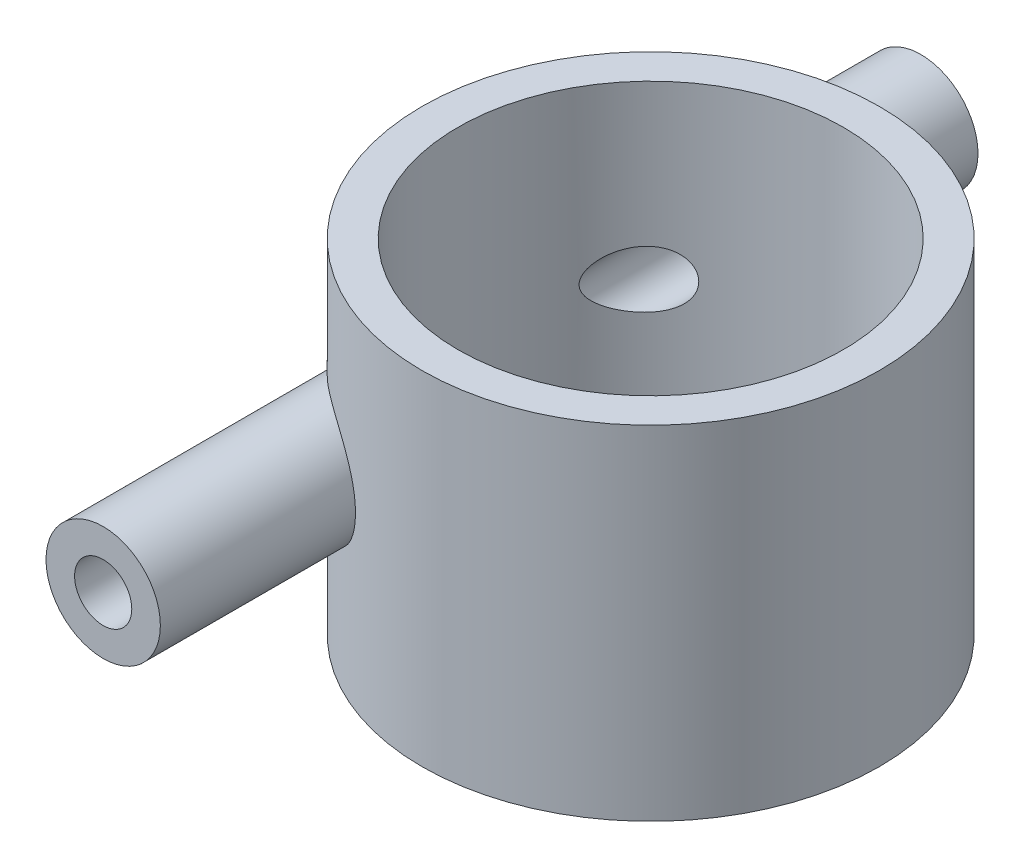
SolidWorks part; units mm, degrees
ref_plane "Front Plane" through (0, 0, 0) normal (0, 0, 1) x (1, 0, 0)
ref_plane "Top Plane" through (0, 0, 0) normal (0, 1, 0) x (1, 0, 0)
ref_plane "Right Plane" through (0, 0, 0) normal (1, 0, 0) x (0, 0, -1)
sketch "Sketch1" plane through (0, 0, 0) normal (0, 1, 0) x (1, 0, 0)
  circle A0 centre (0, 0) radius 12.7
  dimension "D1" = 25.4
extrude "Boss-Extrude1" add sketch "Sketch1" along normal blind 19.05
sketch "Sketch2" plane through (0, 19.05, 0) normal (0, 1, 0) x (1, 0, 0)
  circle A0 centre (0, 0) radius 10.7
  circle A1 centre (0, 0) radius 12.7 construction
  dimension "D1" = 2
extrude "Cut-Extrude1" cut sketch "Sketch2" against normal blind 17.05
ref_plane "Plane1" through (0, 0, 12.7) normal (0, 0, 1) x (1, 0, 0)
sketch "Sketch3" plane through (0, 0, 12.7) normal (0, 0, 1) x (1, 0, 0)
  line L0 (-12.7, 9.525) -> (12.7, 9.525) construction
  line L1 (-12.7, 19.05) -> (-12.7, 0) construction
  line L2 (12.7, 0) -> (12.7, 19.05) construction
  circle A0 centre (-7.7, 9.525) radius 3.175
  circle A1 centre (-7.7, 9.525) radius 1.5875
  dimension "D1" = 5
  dimension "D2" = 6.35
  dimension "D3" = 3.175
extrude "Boss-Extrude2" add sketch "Sketch3" against normal up to surface and the other way blind 10 up to face at (0, 19.05, 12.7)
sketch "Sketch4" plane through (0, 0, 22.7) normal (0, 0, 1) x (1, 0, 0)
  circle A0 centre (-7.7, 9.525) radius 1.5875
  dimension "D1" = 3.175
extrude "Cut-Extrude2" cut sketch "Sketch4" against normal up to surface and the other way through all up to face at (0, 2, 10.7)
mirror "Mirror1" about plane through (0, 0, 0) normal (0, 0, 1) of "Cut-Extrude2", "Boss-Extrude2"
